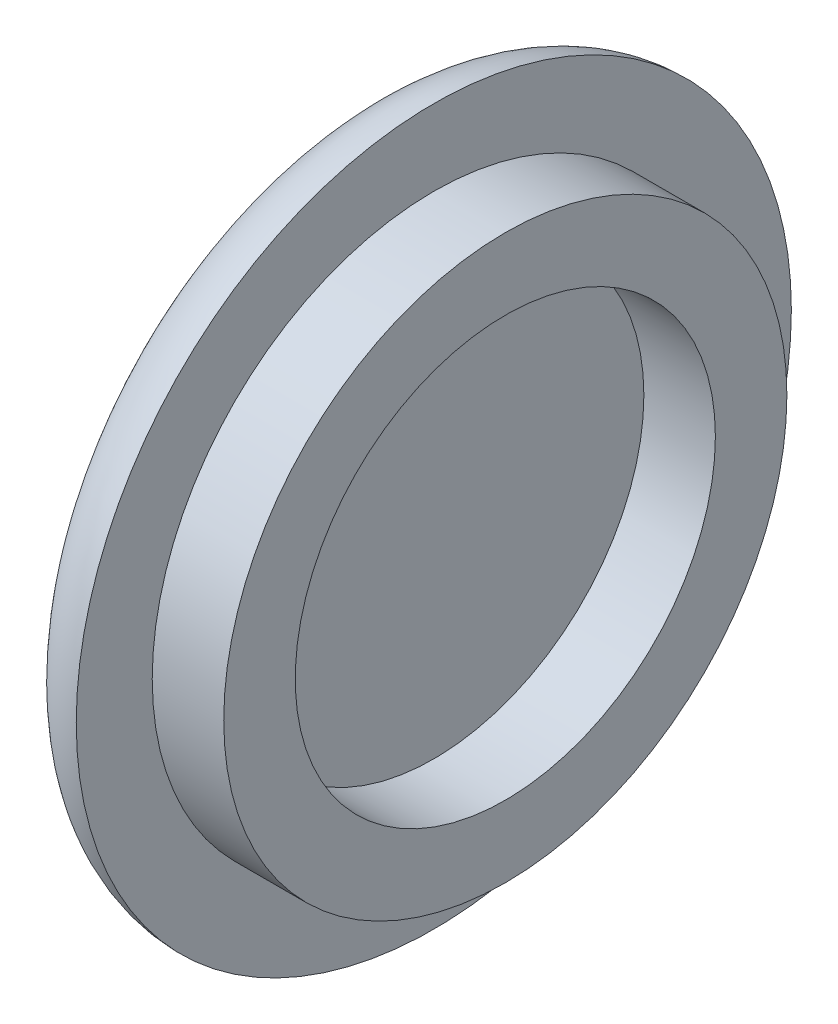
SolidWorks part; units mm, degrees
ref_plane "Front Plane" through (0, 0, 0) normal (0, 0, 1) x (1, 0, 0)
ref_plane "Top Plane" through (0, 0, 0) normal (0, 1, 0) x (1, 0, 0)
ref_plane "Right Plane" through (0, 0, 0) normal (1, 0, 0) x (0, 0, -1)
sketch "Sketch1" plane through (0, 0, 0) normal (1, 0, 0) x (0, 0, -1)
  circle A0 centre (0, 0) radius 7.875
  circle A1 centre (0, 0) radius 10
  dimension "D1" = 15.75
  dimension "D2" = 20
extrude "Boss-Extrude1" add sketch "Sketch1" along normal blind 2 contours A0
extrude "Boss-Extrude2" add sketch "Sketch1<3>" against normal blind 2 contours A1
sketch "Sketch1<3>" plane through (0, 0, 0) normal (1, 0, 0) x (0, 0, -1) same geometry as "Sketch1"
fillet "Fillet1" radius 2 1 edges at (-2, 0, -10)
sketch "Sketch2" plane through (2, 0, 0) normal (1, 0, 0) x (0, 0, -1)
  circle A2 centre (0, 0) radius 5.875
  circle A3 centre (0, 0) radius 5.875
  dimension "D1" = 2
extrude "Cut-Extrude1" cut sketch "Sketch2" against normal blind 2
sketch "Sketch3" plane through (0, 0, 0) normal (1, 0, 0) x (0, 0, -1)
  line L0 (0, 0) -> (0, 10.9102) construction
  line L1 (0, 0) -> (11.5396, 0) construction
pattern_linear "LPattern1" [suppressed] count 4 spacing 23 along (0, -1, 0) count 4 spacing 23 along (0, 0, 1) of bodies 103
